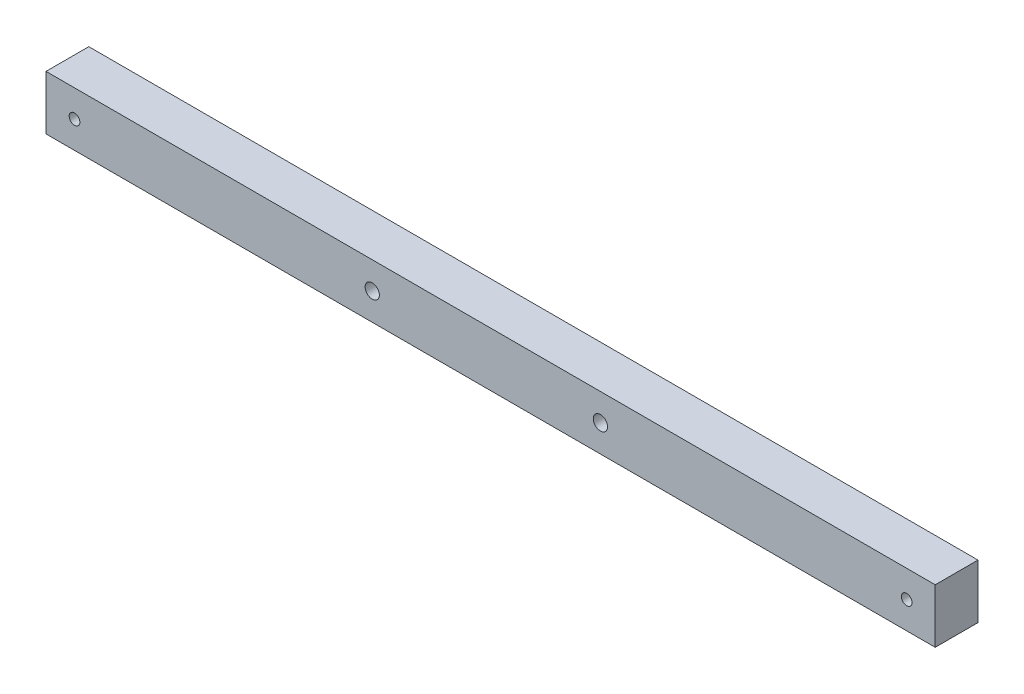
SolidWorks part; units mm, degrees
ref_plane "前视基准面" through (0, 0, 0) normal (0, 0, 1) x (1, 0, 0)
ref_plane "上视基准面" through (0, 0, 0) normal (0, 1, 0) x (1, 0, 0)
ref_plane "右视基准面" through (0, 0, 0) normal (1, 0, 0) x (0, 0, -1)
sketch "草图2" plane through (0, 0, 0) normal (0, 0, 1) x (1, 0, 0)
  line L0 (0, 0) -> (0, -11.1015) construction
  line L1 (-31.175, 1.9) -> (31.175, 1.9)
  line L2 (-31.175, 1.9) -> (-31.175, -1.9)
  line L3 (-31.175, -1.9) -> (31.175, -1.9)
  line L4 (31.175, 1.9) -> (31.175, -1.9)
  line L5 (-31.175, 1.9) -> (31.175, -1.9) construction
  line L6 (-31.175, -1.9) -> (31.175, 1.9) construction
  circle A1 centre (7.7, 0) radius 0.5
  circle A3 centre (-8.3, 0) radius 0.5
  point P0 (0, 0)
  dimension "D3" = 1
  dimension "D5" = 1
  dimension "D4" = 7.7
  dimension "D1" = 3.8
  dimension "D2" = 62.35
  dimension "D7" = 8.3
extrude "凸台-拉伸1" add sketch "草图2" along normal blind 3
sketch "草图3" plane through (0, 0, 0) normal (0, 0, -1) x (-1, 0, 0)
  line L0 (31.175, 1.9) -> (31.175, -1.9) construction
  line L1 (31.175, -1.9) -> (-31.175, -1.9) construction
  line L2 (-31.175, 1.9) -> (31.175, 1.9) construction
  line L3 (29.175, -1.9) -> (29.175, 1.9) construction
  line L4 (-31.175, 0) -> (-29.175, 0) construction
  line L5 (-31.175, -1.9) -> (-31.175, 1.9) construction
  circle A0 centre (29.175, 0) radius 0.375
  circle A1 centre (-29.175, 0) radius 0.375
  dimension "D1" = 0.75
  dimension "D3" = 0.75
  dimension "D2" = 2
  dimension "D4" = 2
extrude "切除-拉伸1" cut sketch "草图3" against normal up to next
